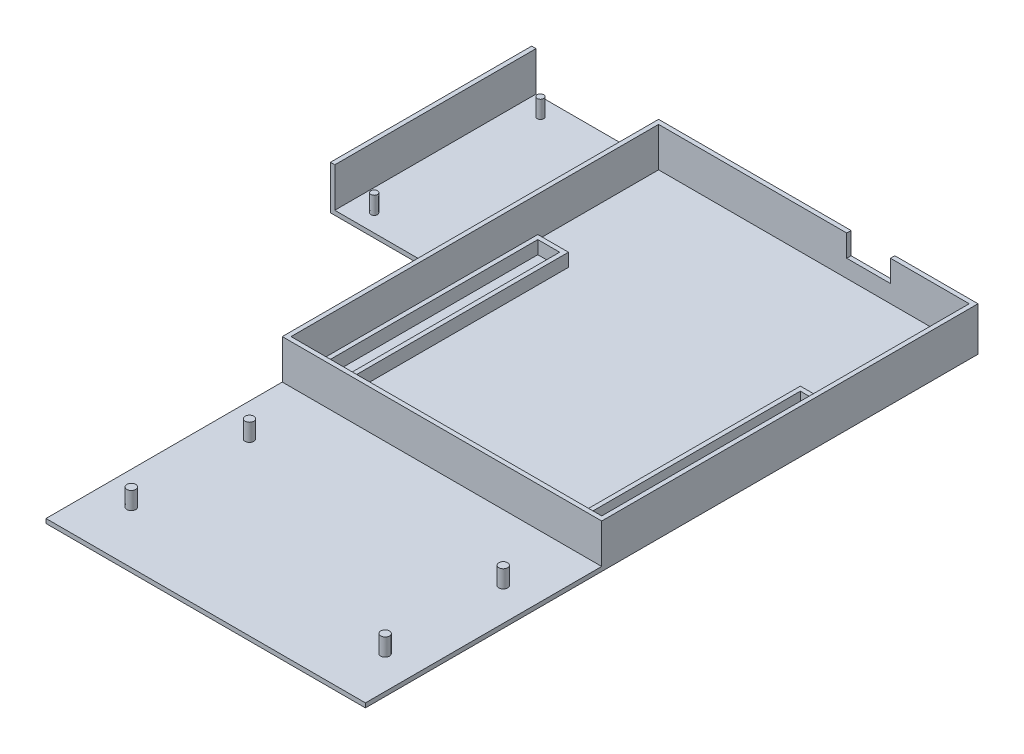
SolidWorks part; units mm, degrees
ref_plane "Спереди" through (0, 0, 0) normal (0, 0, 1) x (1, 0, 0)
ref_plane "Сверху" through (0, 0, 0) normal (0, 1, 0) x (1, 0, 0)
ref_plane "Справа" through (0, 0, 0) normal (1, 0, 0) x (0, 0, -1)
other "Configuration Table"
sketch "Эскиз1" plane through (0, 0, 0) normal (0, 1, 0) x (1, 0, 0)
  line L0 (-1, 85) -> (72, 85)
  line L1 (0, 0) -> (71, 0)
  line L2 (0, 0) -> (0, 84)
  line L3 (0, 84) -> (71, 84)
  line L4 (71, 0) -> (71, 84)
  line L5 (72, -1) -> (72, 85)
  line L6 (-1, -1) -> (72, -1)
  line L7 (-1, -1) -> (-1, 85)
  line L8 (35.5, -1) -> (35.5, 111.8761) construction
  line L9 (3, 3.4) -> (8, 3.4)
  line L10 (3, 3.4) -> (3, 53.4)
  line L11 (3, 53.4) -> (8, 53.4)
  line L12 (8, 3.4) -> (8, 53.4)
  line L13 (63, 3.4) -> (68, 3.4)
  line L14 (63, 3.4) -> (63, 53.4)
  line L15 (63, 53.4) -> (68, 53.4)
  line L16 (68, 3.4) -> (68, 53.4)
  line L17 (2, 54.4) -> (9, 54.4)
  line L18 (-1, -1) -> (72, -1)
  line L19 (-1, -1) -> (-1, -55)
  line L20 (-1, -55) -> (72, -55)
  line L21 (72, -1) -> (72, -55)
  line L22 (-1, 85) -> (-29, 85)
  line L23 (-1, 85) -> (-1, 39)
  line L24 (-1, 39) -> (-29, 39)
  line L25 (-29, 85) -> (-29, 39)
  line L26 (-1, 39) -> (-30, 39)
  line L27 (-1, 39) -> (-1, 85)
  line L28 (-1, 85) -> (-30, 85)
  line L29 (-30, 39) -> (-30, 85)
  line L30 (9, 2.4) -> (9, 54.4)
  line L31 (2, 2.4) -> (9, 2.4)
  line L32 (2, 2.4) -> (2, 54.4)
  line L33 (62, 54.4) -> (69, 54.4)
  line L34 (69, 2.4) -> (69, 54.4)
  line L35 (62, 2.4) -> (69, 2.4)
  line L36 (62, 2.4) -> (62, 54.4)
  circle A0 centre (6.5, -16) radius 1
  circle A1 centre (64.5, -16) radius 1
  circle A2 centre (64.5, -43) radius 1
  circle A3 centre (6.5, -43) radius 1
  circle A4 centre (-24, 81) radius 0.75
  circle A5 centre (-4, 81) radius 0.75
  circle A6 centre (-24, 43) radius 0.75
  circle A7 centre (-4, 43) radius 0.75
  dimension "D9" = 2
  dimension "D13" = 20
  dimension "D17" = 1.5
  dimension "D1" = 84
  dimension "D2" = 71
  dimension "D4" = 65
  dimension "D5" = 5
  dimension "D6" = 3.4
  dimension "D7" = 50
  dimension "D8" = 54
  dimension "D10" = 27
  dimension "D11" = 58
  dimension "D12" = 15
  dimension "D14" = 38
  dimension "D15" = 28
  dimension "D16" = 3
  dimension "D18" = 4
  dimension "D19" = 46
  dimension "D21" = 1
  dimension "D3" = 1
  dimension "D22" = 1
extrude "Бобышка-Вытянуть1" add sketch "Эскиз1" along normal blind 1 contours L22 L25 L24 L7 A7 A6 A5 A4 | L1 L8 L3 L2 L31 L32 L17 L30 | L8 L1 L4 L3 L35 L36 L33 L34 | L21 L18 L6 L19 L20 A3 A2 A1 A0 | L8 L18 L5 L0 L3 L4 L1 | L6 L8 L1 L2 L3 L0 L7 | L32 L31 L30 L17 L12 L9 L10 L11 | L9 L12 L11 L10 | L36 L35 L34 L33 L16 L13 L14 L15 | L13 L16 L15 L14 region at (17.25, 0, -84.0657) region at (-15.0055, 0, -62) region at (53.75, 0, -84.0657) region at (19.4532, 0, -43.8909) region at (51.5468, 0, -43.8909) region at (35.5, 0, 27.9952) region at (5.5, 0, -28.4) region at (65.5, 0, -28.4) region at (5.5, 0, -53.8753) region at (65.5, 0, -53.8753)
extrude "Бобышка-Вытянуть2" add sketch "Эскиз1<3>" along normal blind 10 contours L29 L26 L7 L24 L25 L28 | L6 L8 L1 L2 L3 L0 L7 | L8 L18 L5 L0 L3 L4 L1 region at (17.25, 0, -84.0657) region at (53.75, 0, -84.0657) region at (-29.5, 0, -62)
sketch "Эскиз1<3>" plane through (0, 0, 0) normal (0, 1, 0) x (1, 0, 0) same geometry as "Эскиз1"
extrude "Бобышка-Вытянуть3" add sketch "Эскиз1<4>" along normal blind 4 contours L32 L31 L30 L17 L12 L9 L10 L11 | L36 L35 L34 L33 L16 L13 L14 L15 region at (5.5, 0, -53.8753) region at (65.5, 0, -53.8753)
sketch "Эскиз1<4>" plane through (0, 0, 0) normal (0, 1, 0) x (1, 0, 0) same geometry as "Эскиз1"
extrude "Бобышка-Вытянуть4" add sketch "Эскиз1<5>" along normal blind 5 contours A7 | A6 | A4 | A5 | A0 | A1 | A2 | A3 region at (-24, 0, -81) region at (-4, 0, -81) region at (-24, 0, -43) region at (-4, 0, -43)
sketch "Эскиз1<5>" plane through (0, 0, 0) normal (0, 1, 0) x (1, 0, 0) same geometry as "Эскиз1"
sketch "Эскиз2" plane through (0, 0, -84) normal (0, 0, 1) x (1, 0, 0)
  line L0 (-1, 10) -> (72, 10) construction
  line L1 (53, 10) -> (43, 10)
  line L2 (53, 10) -> (53, 5)
  line L3 (53, 5) -> (43, 5)
  line L4 (43, 10) -> (43, 5)
  line L5 (72, 10) -> (72, 0) construction
  dimension "D1" = 5
  dimension "D2" = 10
  dimension "D3" = 19
extrude "Вырез-Вытянуть2" cut sketch "Эскиз2" against normal blind 10
